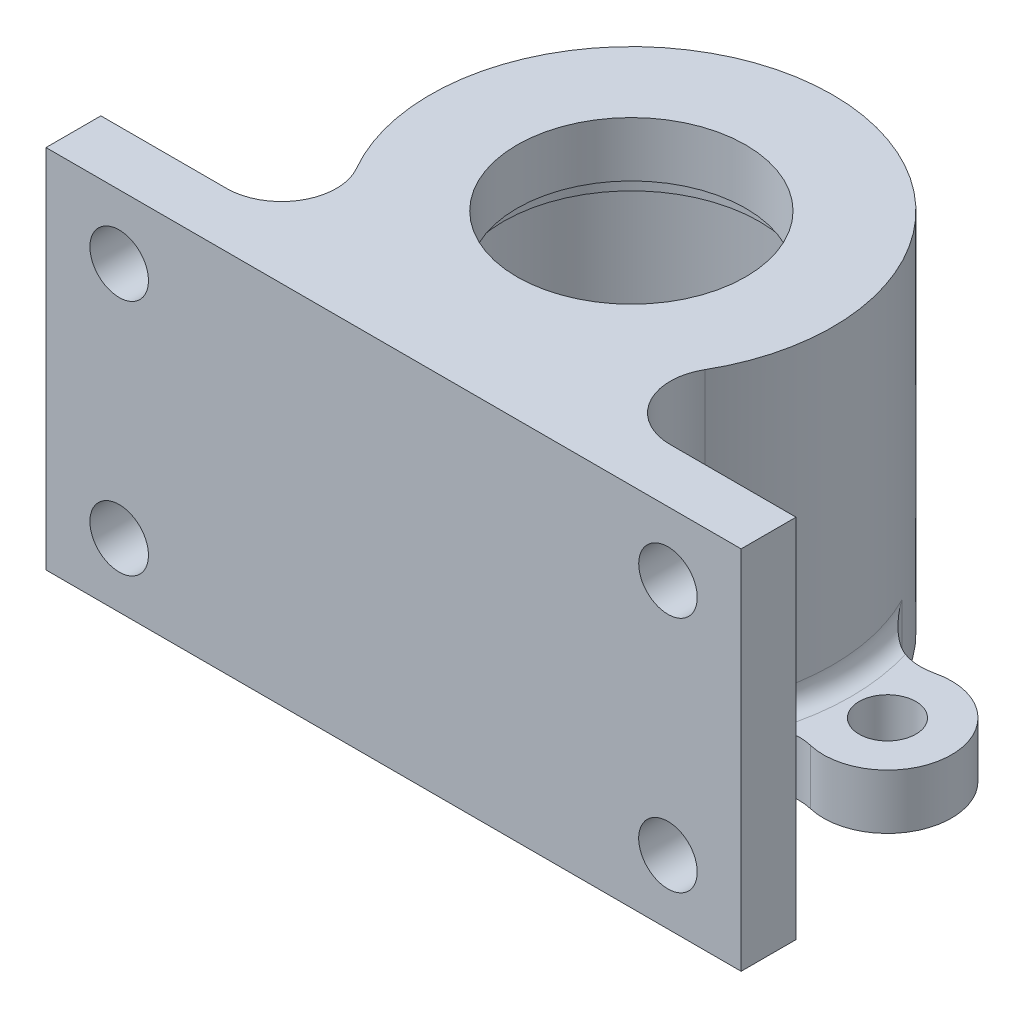
SolidWorks part; units mm, degrees
ref_plane "前视基准面" through (0, 0, 0) normal (0, 0, 1) x (1, 0, 0)
ref_plane "上视基准面" through (0, 0, 0) normal (0, 1, 0) x (1, 0, 0)
ref_plane "右视基准面" through (0, 0, 0) normal (1, 0, 0) x (0, 0, -1)
sketch "草图1" plane through (0, 0, 0) normal (0, 1, 0) x (1, 0, 0)
  circle A0 centre (0, 0) radius 11
  dimension "D1" = 22
extrude "凸台-拉伸1" add sketch "草图1" along normal blind 20
sketch "草图2" plane through (0, 20, 0) normal (0, 1, 0) x (1, 0, 0)
  circle A0 centre (0, 0) radius 6.25
  dimension "D1" = 12.5
extrude "切除-拉伸1" cut sketch "草图2" against normal up to next
sketch "草图3" plane through (0, 0, 0) normal (0, -1, 0) x (1, 0, 0)
  circle A0 centre (0, 0) radius 9.2
  dimension "D1" = 18.4
extrude "切除-拉伸2" cut sketch "草图3" against normal offset from surface (16 mm away) 4 up to face at (0, 20, 6.25)
ref_plane "基准面1" through (0, 0, 13) normal (0, 0, 1) x (1, 0, 0)
sketch "草图7" plane through (0, 0, 13) normal (0, 0, 1) x (1, 0, 0)
  line L0 (0, 29.0003) -> (0, -9.2145) construction
  line L1 (11, 20) -> (-11, 20) construction
  line L2 (-19, 0) -> (19, 0)
  line L3 (-19, 0) -> (-19, 20)
  line L4 (-19, 20) -> (19, 20)
  line L5 (19, 0) -> (19, 20)
  line L6 (-19, 0) -> (19, 20) construction
  line L7 (-19, 20) -> (19, 0) construction
  point P3 (0, 10)
  dimension "D1" = 20
  dimension "D2" = 38
extrude "凸台-拉伸3" add sketch "草图7" against normal blind 3 separate body
sketch "草图8" plane through (0, 20, 0) normal (0, 1, 0) x (1, 0, 0)
  line L0 (0, -2.063) -> (0, -19.6358) construction
  line L1 (19, -10) -> (-19, -10) construction
  line L2 (12.1244, -10) -> (-12.1244, -10)
  arc A0 (9.5263, -5.5) -> (12.1244, -10) centre (12.1244, -7) ccw
  circle A1 centre (0, 0) radius 11 construction
  arc A2 (-9.5263, -5.5) -> (9.5263, -5.5) centre (0, 0) ccw
  arc A3 (-9.5263, -5.5) -> (-12.1244, -10) centre (-12.1244, -7) cw
  line M6 (19, -10) -> (-19, -10)
  dimension "D1" = 6
extrude "凸台-拉伸4" add sketch "草图8" against normal up to surface (20 mm away) contours A2 A3 L2 | A2 A0 M6 region at (-8.2013, 20, 8.9207) region at (8.2013, 20, 8.9207) up to face at (0, 0, -9.2)
sketch "草图9" plane through (0, 0, 13) normal (0, 0, 1) x (1, 0, 0)
  line L0 (0, 24.9971) -> (0, -4.9971) construction
  line L1 (-19, 10) -> (21.2164, 10) construction
  line L2 (-19, 20) -> (-19, 0) construction
  circle A0 centre (-15, 16.5) radius 1.6
  circle A1 centre (15, 16.5) radius 1.6
  circle A2 centre (-15, 3.5) radius 1.6
  circle A3 centre (15, 3.5) radius 1.6
  dimension "D1" = 3.2
  dimension "D2" = 13
  dimension "D3" = 30
extrude "切除-拉伸4" cut sketch "草图9" against normal up to next
sketch "草图10" plane through (0, 0, 0) normal (0, -1, 0) x (1, 0, 0)
  line L0 (-13.5909, 0) -> (16.1793, 0) construction
  line L1 (0, 10.2732) -> (0, -10.5517) construction
  line L2 (14, 0) -> (0, 0) construction
  circle A0 centre (14, 0) radius 1.55
  arc A1 (13.1875, -3.4044) -> (13.1875, 3.4044) centre (14, 0) ccw
  arc A2 (9.8144, 4.9676) -> (13.1875, 3.4044) centre (12.4911, 6.3224) ccw
  circle A3 centre (0, 0) radius 11 construction
  arc A4 (9.8144, -4.9676) -> (13.1875, -3.4044) centre (12.4911, -6.3224) cw
  circle A5 centre (-14, 0) radius 1.55
  arc A6 (-9.8144, 4.9676) -> (-9.8144, -4.9676) centre (0, 0) ccw
  arc A7 (-13.1875, -3.4044) -> (-13.1875, 3.4044) centre (-14, 0) cw
  arc A8 (-9.8144, 4.9676) -> (-13.1875, 3.4044) centre (-12.4911, 6.3224) cw
  arc A9 (9.8144, -4.9676) -> (9.8144, 4.9676) centre (0, 0) ccw
  arc A10 (-9.8144, -4.9676) -> (-13.1875, -3.4044) centre (-12.4911, -6.3224) ccw
  arc M6 (-9.5263, 5.5) -> (9.5263, 5.5) centre (0, 0) ccw
  dimension "D1" = 3.1
  dimension "D2" = 7
  dimension "D5" = 6
  dimension "D3" = 90
  dimension "D4" = 14
extrude "凸台-拉伸5" add sketch "草图10" against normal blind 3 contours A10 A8 A7 A5 M6 | A4 A1 A2 A0 M6 region at (11.1768, 0, -3.4866) region at (-11.1768, 0, -3.4866)
fillet "圆角3" radius 1 2 edges at (-11, 3, 0) (11, 3, 0)
sketch "草图11" plane through (0, 16, 0) normal (0, -1, 0) x (1, 0, 0)
  circle A0 centre (0, 0) radius 7
  dimension "D1" = 14
extrude "切除-拉伸5" cut sketch "草图11" against normal blind 1
